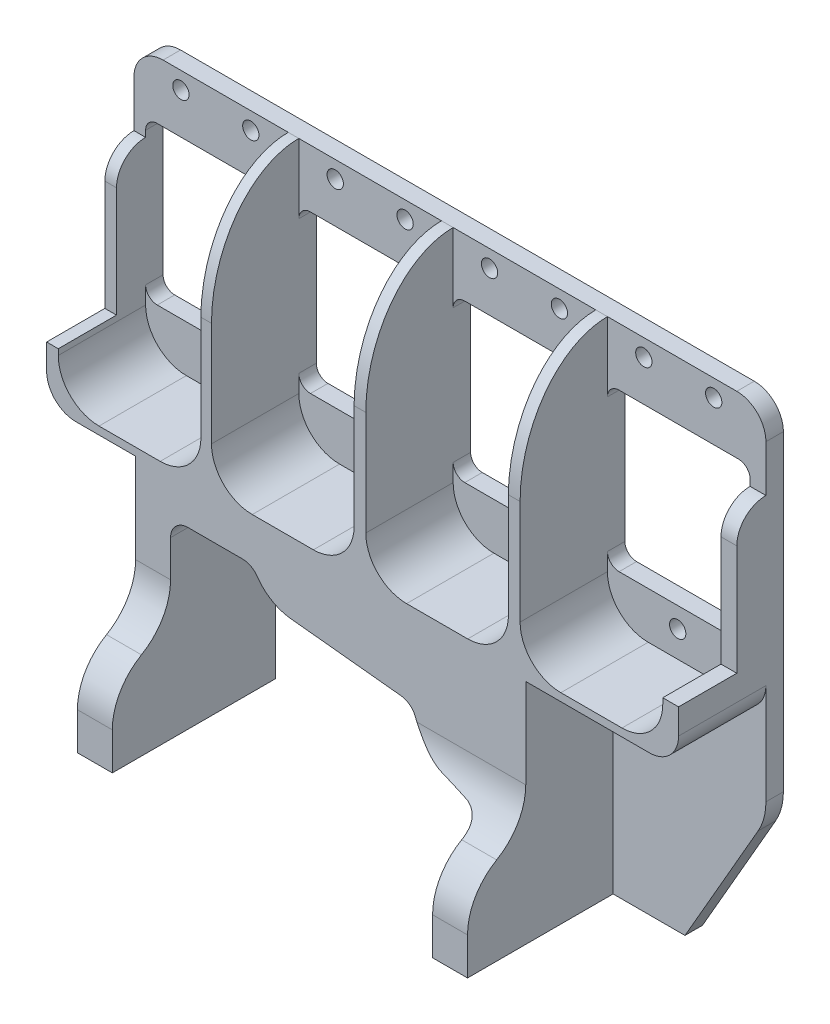
SolidWorks part; units mm, degrees
ref_plane "前视基准面" through (0, 0, 0) normal (0, 0, 1) x (1, 0, 0)
ref_plane "上视基准面" through (0, 0, 0) normal (0, 1, 0) x (1, 0, 0)
ref_plane "右视基准面" through (0, 0, 0) normal (1, 0, 0) x (0, 0, -1)
other "Configuration Table"
sketch "草图2" plane through (0, 0, 0) normal (0, 0, 1) x (1, 0, 0)
  line L0 (151.0633, 209.0132) -> (151.0476, 168.4956)
  line L1 (178.2976, 201.2948) -> (178.2976, 178.2948)
  line L2 (178.2976, 178.2948) -> (178.2976, 175.2948)
  line L3 (206.1919, 197.3972) -> (206.1919, 171.3972)
  line L4 (194.4691, 218.3694) -> (201.3108, 217.5164)
  line L5 (201.3108, 217.5164) -> (208.7441, 216.356)
  line L6 (166.5748, 222.2669) -> (173.4165, 221.4139)
  line L261 (199.1919, 164.3972) -> (192.9419, 164.3972)
  line L262 (237.2256, 158.3592) -> (242.1719, 178.962)
  line L263 (236.0401, 178.625) -> (234.6391, 165.2957)
  line L264 (225.8467, 158.1757) -> (217.3932, 159.0642)
  line L266 (210.2733, 167.8566) -> (212.2453, 186.6193)
  line L267 (252.608, 147.4673) -> (245.8094, 149.0995)
  line L268 (263.7227, 151.9978) -> (271.0421, 182.4855)
  line L269 (188.6919, 164.3972) -> (192.9419, 164.3972)
  line L270 (265.6404, 180.333) -> (245.7068, 185.1186)
  line L271 (252.8645, 197.798) -> (254.0666, 202.8051)
  line L272 (265.506, 196.9076) -> (265.0192, 194.88)
  line L273 (242.1719, 178.962) -> (243.2952, 183.6408)
  line L274 (187.6765, 215.8498) -> (187.692, 213.3583)
  line L275 (200.1917, 213.4362) -> (200.1725, 216.5198)
  line L276 (183.6919, 199.3972) -> (204.1919, 199.3972)
  line L278 (212.2623, 167.6475) -> (232.65, 165.5047)
  line L279 (220.5261, 208.0048) -> (221.0496, 212.986)
  line L280 (235.4723, 192.3568) -> (215.0846, 194.4996)
  line L281 (233.2553, 209.5307) -> (232.9576, 206.6982)
  line L282 (236.0401, 178.625) -> (237.2523, 190.1587)
  line L283 (212.8865, 192.7196) -> (212.2453, 186.6193)
  line L284 (183.6919, 172.3972) -> (204.1919, 172.3972)
  line L285 (239.4038, 158.8646) -> (259.3374, 154.079)
  line L286 (262.7567, 147.974) -> (251.8225, 127.8461)
  line L287 (263.7227, 151.9978) -> (262.7567, 147.974)
  line L288 (181.6919, 197.3972) -> (181.6919, 174.3972)
  line L289 (181.6919, 171.3972) -> (181.6919, 174.3972)
  line L290 (267.1183, 177.9214) -> (261.0487, 152.6398)
  line L291 (171.2976, 168.2948) -> (165.0476, 168.2948)
  line L293 (160.7976, 168.2948) -> (165.0476, 168.2948)
  line L295 (159.7822, 219.7473) -> (159.7977, 217.2558)
  line L296 (172.2974, 217.3337) -> (172.2782, 220.4173)
  line L297 (155.7976, 203.2948) -> (176.2976, 203.2948)
  line L300 (155.7976, 176.2948) -> (176.2976, 176.2948)
  line L301 (153.7976, 201.2948) -> (153.7976, 178.2948)
  line L302 (153.7976, 175.2948) -> (153.7976, 178.2948)
  line L303 (173.4165, 221.4139) -> (194.4691, 218.3694)
  line L304 (187.6765, 215.8498) -> (187.6765, 218.2449)
  line L305 (187.6765, 218.2449) -> (186.8438, 219.4721)
  line L306 (234.2789, 127.8461) -> (251.8225, 127.8461)
  line L307 (233.4789, 133.8446) -> (233.4789, 127.8461)
  line L308 (233.4789, 127.8461) -> (234.2789, 127.8461)
  line L309 (178.4789, 128.6348) -> (178.4789, 135.1402)
  line L310 (172.4789, 127.8461) -> (173.1594, 127.8461)
  line L311 (178.4789, 127.8461) -> (178.4789, 128.6348)
  line L312 (177.6789, 127.8461) -> (178.4789, 127.8461)
  line L313 (173.1594, 127.8461) -> (177.6789, 127.8461)
  line L314 (233.4789, 143.0663) -> (233.4789, 140.4276)
  line L315 (178.4789, 135.1402) -> (178.4789, 139.2823)
  line L316 (178.4789, 139.2823) -> (178.4789, 146.9191)
  line L317 (178.4789, 146.9191) -> (178.4789, 157.8461)
  line L318 (199.0973, 156.1096) -> (218.0428, 154.1184)
  line L319 (181.4789, 160.8461) -> (190.8607, 160.8461)
  line L320 (151.0476, 168.4956) -> (172.4789, 127.8461)
  arc A276 (237.2256, 158.3592) -> (238.6979, 152.1924) centre (244.0322, 156.725) ccw
  arc A277 (210.2733, 167.8566) -> (217.3932, 159.0642) centre (218.2295, 167.0204) ccw
  arc A278 (199.1919, 164.3972) -> (206.1919, 171.3972) centre (199.1919, 171.3972) ccw
  arc A279 (225.8467, 158.1757) -> (234.6391, 165.2957) centre (226.6829, 166.1319) ccw
  arc A281 (242.1719, 178.962) -> (242.2118, 179.1563) centre (239.2548, 179.6624) ccw
  arc A282 (212.2453, 186.6193) -> (212.2566, 186.7575) centre (209.2618, 186.9329) ccw
  arc A283 (236.0666, 178.8175) -> (236.0401, 178.625) centre (239.0236, 178.3114) ccw
  arc A284 (246.0441, 206.6986) -> (242.0035, 208.0676) centre (168.9419, -14.234) ccw
  arc A285 (220.2745, 214.0661) -> (208.7441, 216.356) centre (168.9419, -14.234) ccw
  arc A286 (252.608, 147.4673) -> (261.0487, 152.6398) centre (254.2421, 154.2739) ccw
  arc A287 (181.6919, 171.3972) -> (188.6919, 164.3972) centre (188.6919, 171.3972) ccw
  circle A288 centre (251.4735, 190.9331) radius 1.4
  circle A289 centre (263.142, 188.1317) radius 1.4
  arc A290 (267.1183, 177.9214) -> (265.6404, 180.333) centre (265.1735, 178.3883) ccw
  arc A291 (245.7068, 185.1186) -> (243.2952, 183.6408) centre (245.2399, 183.1739) ccw
  arc A292 (254.0666, 202.8051) -> (253.4554, 203.971) centre (253.0943, 203.0385) ccw
  arc A293 (252.8645, 197.798) -> (265.0192, 194.88) centre (258.9419, 196.339) ccw
  arc A294 (267.1505, 197.4145) -> (265.506, 196.9076) centre (266.4783, 196.6741) ccw
  arc A295 (253.4554, 203.971) -> (246.0441, 206.6986) centre (168.9419, -14.234) ccw
  arc A296 (271.7032, 188.063) -> (267.1505, 197.4145) centre (257.74, 187.0491) ccw
  arc A297 (187.692, 213.3583) -> (200.1917, 213.4362) centre (193.9419, 213.3972) ccw
  arc A298 (201.3108, 217.5164) -> (200.1725, 216.5198) centre (201.1725, 216.526) ccw
  arc A299 (206.1919, 197.3972) -> (204.1919, 199.3972) centre (204.1919, 197.3972) ccw
  arc A300 (183.6919, 199.3972) -> (181.6919, 197.3972) centre (183.6919, 197.3972) ccw
  circle A301 centre (199.9419, 206.3972) radius 1.4
  circle A302 centre (187.9419, 206.3972) radius 1.4
  arc A304 (210.4824, 169.8456) -> (212.2623, 167.6475) centre (212.4714, 169.6366) ccw
  arc A305 (232.65, 165.5047) -> (234.8481, 167.2847) centre (232.8591, 167.4938) ccw
  circle A306 centre (222.0903, 163.0953) radius 1.4
  arc A307 (220.5261, 208.0048) -> (232.9576, 206.6982) centre (226.7419, 207.3515) ccw
  circle A308 centre (220.043, 201.017) radius 1.4
  circle A309 centre (231.9773, 199.7627) radius 1.4
  arc A310 (237.2523, 190.1587) -> (235.4723, 192.3568) centre (235.2632, 190.3678) ccw
  arc A311 (221.0496, 212.986) -> (220.2745, 214.0661) centre (220.0551, 213.0905) ccw
  arc A312 (234.5301, 210.386) -> (233.2553, 209.5307) centre (234.2498, 209.4261) ccw
  arc A313 (215.0846, 194.4996) -> (212.8865, 192.7196) centre (214.8756, 192.5106) ccw
  arc A314 (242.0038, 208.0674) -> (234.5301, 210.386) centre (168.9419, -14.234) ccw
  arc A315 (204.1919, 172.3972) -> (206.1919, 174.3972) centre (204.1919, 174.3972) ccw
  circle A316 centre (193.9419, 168.8972) radius 1.4
  arc A317 (181.6919, 174.3972) -> (183.6919, 172.3972) centre (183.6919, 174.3972) ccw
  arc A318 (259.3374, 154.079) -> (261.749, 155.5569) centre (259.8043, 156.0238) ccw
  arc A319 (237.926, 161.2763) -> (239.4038, 158.8646) centre (239.8707, 160.8094) ccw
  circle A320 centre (248.5535, 153.0685) radius 1.4
  circle A321 centre (193.9419, 213.3972) radius 3.5
  circle A323 centre (258.9419, 196.339) radius 3.5
  arc A324 (263.3908, 199.858) -> (253.4554, 203.971) centre (168.9419, -14.234) ccw
  arc A325 (267.1505, 197.4145) -> (263.3908, 199.858) centre (257.74, 187.0491) ccw
  circle A326 centre (226.7419, 207.3515) radius 3.5
  arc A327 (234.5301, 210.386) -> (220.2745, 214.0661) centre (168.9419, -14.234) ccw
  arc A328 (171.2976, 168.2948) -> (178.2976, 175.2948) centre (171.2976, 175.2948) ccw
  arc A331 (153.7976, 175.2948) -> (160.7976, 168.2948) centre (160.7976, 175.2948) ccw
  arc A332 (159.7822, 219.7473) -> (158.3002, 220.6173) centre (158.7822, 219.7411) ccw
  arc A333 (159.7977, 217.2558) -> (172.2974, 217.3337) centre (166.0476, 217.2948) ccw
  arc A334 (173.4165, 221.4139) -> (172.2782, 220.4173) centre (173.2782, 220.4235) ccw
  arc A335 (178.2976, 201.2948) -> (176.2976, 203.2948) centre (176.2976, 201.2948) ccw
  arc A336 (155.7976, 203.2948) -> (153.7976, 201.2948) centre (155.7976, 201.2948) ccw
  circle A337 centre (172.0476, 210.2948) radius 1.4
  circle A338 centre (160.0476, 210.2948) radius 1.4
  arc A339 (158.3002, 220.6173) -> (152.4939, 214.5477) centre (165.0476, 208.3505) ccw
  arc A340 (176.2976, 176.2948) -> (178.2976, 178.2948) centre (176.2976, 178.2948) ccw
  circle A341 centre (166.0476, 172.7948) radius 1.4
  arc A342 (153.7976, 178.2948) -> (155.7976, 176.2948) centre (155.7976, 178.2948) ccw
  circle A343 centre (166.0476, 217.2948) radius 3.5
  arc A345 (166.5748, 222.2669) -> (158.3002, 220.6173) centre (165.0476, 208.3505) ccw
  arc A346 (220.5415, 152.1792) -> (221.76, 150.0096) centre (228.0411, 154.9641) ccw
  arc A347 (193.3351, 159.5424) -> (199.0973, 156.1096) centre (199.9335, 164.0658) ccw
  arc A348 (220.5415, 152.1792) -> (218.0428, 154.1184) centre (217.7292, 151.1348) ccw
  arc A349 (193.3351, 159.5424) -> (190.8607, 160.8461) centre (190.8607, 157.8461) ccw
  arc A350 (181.4789, 160.8461) -> (178.4789, 157.8461) centre (181.4789, 157.8461) ccw
  spline S5 degree 3 poles (245.8094, 149.0995) (244.7023, 149.3653) (243.562, 149.639) (242.3981, 149.9185) knots 0 0 0 0 1 1 1 1
  spline S6 degree 3 poles (242.3981, 149.9185) (240.9661, 150.2604) (239.6561, 151.0615) (238.6979, 152.1924) knots 0 0 0 0 1 1 1 1
  spline S7 degree 3 poles (271.0421, 182.4855) (271.1468, 182.9215) (271.2515, 183.3575) (271.3531, 183.7809) knots 0 0 0 0 1 1 1 1
  spline S8 degree 3 poles (271.3531, 183.7809) (271.6392, 184.9581) (271.73, 186.0745) (271.7435, 187.2429) (271.7328, 187.5457) (271.7129, 187.9558) (271.7023, 188.0633) (271.7026, 188.063) knots 0 0 0 0 0.5 0.5 0.75 0.75 1 1 1 1
  spline S9 degree 3 poles (152.4939, 214.5476) (152.4935, 214.5473) (152.4251, 214.4133) (152.183, 213.882) (152.0119, 213.4848) (151.6571, 212.4716) (151.4748, 211.8536) (151.1955, 210.4931) (151.098, 209.7566) (151.0633, 209.0132) knots 0 0 0 0 0.25 0.25 0.5 0.5 0.75 0.75 1 1 1 1
  spline S10 degree 3 poles (233.4789, 140.4276) (233.4789, 138.7088) (233.4789, 136.2853) (233.4789, 133.8446) knots 0 0 0 0 1 1 1 1
  spline S11 degree 3 poles (233.2337, 144.2542) (233.3952, 143.8804) (233.4792, 143.4735) (233.4789, 143.0663) knots 0 0 0 0 1 1 1 1
  spline S12 degree 3 poles (231.1793, 145.9834) (231.6902, 145.8625) (232.1463, 145.6054) (232.8415, 144.9724) (233.0819, 144.6067) (233.2337, 144.2542) knots 0 0 0 0 0.5 0.5 1 1 1 1
  spline S13 degree 3 poles (226.1736, 147.1852) (227.9043, 146.7697) (229.5835, 146.3665) (231.1793, 145.9834) knots 0 0 0 0 1 1 1 1
  spline S14 degree 3 poles (221.76, 150.0096) (222.8696, 148.5987) (224.4447, 147.5969) (226.1736, 147.1852) knots 0 0 0 0 1 1 1 1
  point P0 (0, 0)
  line B0 (187.9419, 206.3972) -> (187.9419, 208.8972)
  line B1 (187.9419, 206.3972) -> (185.4419, 206.3972)
  line B2 (187.9419, 206.3972) -> (187.9419, 203.8972)
  line B3 (187.9419, 206.3972) -> (190.4419, 206.3972)
  line B4 (187.9419, 208.8972) -> (187.9419, 210.2972)
  line B5 (185.4419, 206.3972) -> (184.0419, 206.3972)
  line B6 (187.9419, 203.8972) -> (187.9419, 202.4972)
  line B7 (190.4419, 206.3972) -> (191.8419, 206.3972)
  line B8 (222.0903, 163.0953) -> (222.0903, 165.5953)
  line B9 (222.0903, 163.0953) -> (219.5903, 163.0953)
  line B10 (222.0903, 163.0953) -> (222.0903, 160.5953)
  line B11 (222.0903, 163.0953) -> (224.5903, 163.0953)
  line B12 (222.0903, 165.5953) -> (222.0903, 166.9953)
  line B13 (219.5903, 163.0953) -> (218.1903, 163.0953)
  line B14 (222.0903, 160.5953) -> (222.0903, 159.1953)
  line B15 (224.5903, 163.0953) -> (225.9903, 163.0953)
  line B16 (251.4735, 190.9331) -> (251.4735, 193.4331)
  line B17 (251.4735, 190.9331) -> (248.9735, 190.9331)
  line B18 (251.4735, 190.9331) -> (251.4735, 188.4331)
  line B19 (251.4735, 190.9331) -> (253.9735, 190.9331)
  line B20 (251.4735, 193.4331) -> (251.4735, 194.8331)
  line B21 (248.9735, 190.9331) -> (247.5735, 190.9331)
  line B22 (251.4735, 188.4331) -> (251.4735, 187.0331)
  line B23 (253.9735, 190.9331) -> (255.3735, 190.9331)
  line B24 (263.142, 188.1317) -> (263.142, 190.6317)
  line B25 (263.142, 188.1317) -> (260.642, 188.1317)
  line B26 (263.142, 188.1317) -> (263.142, 185.6317)
  line B27 (263.142, 188.1317) -> (265.642, 188.1317)
  line B28 (263.142, 190.6317) -> (263.142, 192.0317)
  line B29 (260.642, 188.1317) -> (259.242, 188.1317)
  line B30 (263.142, 185.6317) -> (263.142, 184.2317)
  line B31 (265.642, 188.1317) -> (267.042, 188.1317)
  line B32 (248.5535, 153.0685) -> (248.5535, 155.5685)
  line B33 (248.5535, 153.0685) -> (246.0535, 153.0685)
  line B34 (248.5535, 153.0685) -> (248.5535, 150.5685)
  line B35 (248.5535, 153.0685) -> (251.0535, 153.0685)
  line B36 (248.5535, 155.5685) -> (248.5535, 156.9685)
  line B37 (246.0535, 153.0685) -> (244.6535, 153.0685)
  line B38 (248.5535, 150.5685) -> (248.5535, 149.1685)
  line B39 (251.0535, 153.0685) -> (252.4535, 153.0685)
  line B40 (231.9773, 199.7627) -> (231.9773, 202.2627)
  line B41 (231.9773, 199.7627) -> (229.4773, 199.7627)
  line B42 (231.9773, 199.7627) -> (231.9773, 197.2627)
  line B43 (231.9773, 199.7627) -> (234.4773, 199.7627)
  line B44 (231.9773, 202.2627) -> (231.9773, 203.6627)
  line B45 (229.4773, 199.7627) -> (228.0773, 199.7627)
  line B46 (231.9773, 197.2627) -> (231.9773, 195.8627)
  line B47 (234.4773, 199.7627) -> (235.8773, 199.7627)
  line B48 (220.043, 201.017) -> (220.043, 203.517)
  line B49 (220.043, 201.017) -> (217.543, 201.017)
  line B50 (220.043, 201.017) -> (220.043, 198.517)
  line B51 (220.043, 201.017) -> (222.543, 201.017)
  line B52 (220.043, 203.517) -> (220.043, 204.917)
  line B53 (217.543, 201.017) -> (216.143, 201.017)
  line B54 (220.043, 198.517) -> (220.043, 197.117)
  line B55 (222.543, 201.017) -> (223.943, 201.017)
  line B56 (193.9419, 168.8972) -> (193.9419, 171.3972)
  line B57 (193.9419, 168.8972) -> (191.4419, 168.8972)
  line B58 (193.9419, 168.8972) -> (193.9419, 166.3972)
  line B59 (193.9419, 168.8972) -> (196.4419, 168.8972)
  line B60 (193.9419, 171.3972) -> (193.9419, 172.7972)
  line B61 (191.4419, 168.8972) -> (190.0419, 168.8972)
  line B62 (193.9419, 166.3972) -> (193.9419, 164.9972)
  line B63 (196.4419, 168.8972) -> (197.8419, 168.8972)
  line B64 (199.9419, 206.3972) -> (199.9419, 208.8972)
  line B65 (199.9419, 206.3972) -> (197.4419, 206.3972)
  line B66 (199.9419, 206.3972) -> (199.9419, 203.8972)
  line B67 (199.9419, 206.3972) -> (202.4419, 206.3972)
  line B68 (199.9419, 208.8972) -> (199.9419, 210.2972)
  line B69 (197.4419, 206.3972) -> (196.0419, 206.3972)
  line B70 (199.9419, 203.8972) -> (199.9419, 202.4972)
  line B71 (202.4419, 206.3972) -> (203.8419, 206.3972)
  line B72 (160.0476, 210.2948) -> (160.0476, 212.7948)
  line B73 (160.0476, 210.2948) -> (157.5476, 210.2948)
  line B74 (160.0476, 210.2948) -> (160.0476, 207.7948)
  line B75 (160.0476, 210.2948) -> (162.5476, 210.2948)
  line B76 (160.0476, 212.7948) -> (160.0476, 214.1948)
  line B77 (157.5476, 210.2948) -> (156.1476, 210.2948)
  line B78 (160.0476, 207.7948) -> (160.0476, 206.3948)
  line B79 (162.5476, 210.2948) -> (163.9476, 210.2948)
  line B80 (166.0476, 172.7948) -> (166.0476, 175.2948)
  line B81 (166.0476, 172.7948) -> (163.5476, 172.7948)
  line B82 (166.0476, 172.7948) -> (166.0476, 170.2948)
  line B83 (166.0476, 172.7948) -> (168.5476, 172.7948)
  line B84 (166.0476, 175.2948) -> (166.0476, 176.6948)
  line B85 (163.5476, 172.7948) -> (162.1476, 172.7948)
  line B86 (166.0476, 170.2948) -> (166.0476, 168.8948)
  line B87 (168.5476, 172.7948) -> (169.9476, 172.7948)
  line B88 (172.0476, 210.2948) -> (172.0476, 212.7948)
  line B89 (172.0476, 210.2948) -> (169.5476, 210.2948)
  line B90 (172.0476, 210.2948) -> (172.0476, 207.7948)
  line B91 (172.0476, 210.2948) -> (174.5476, 210.2948)
  line B92 (172.0476, 212.7948) -> (172.0476, 214.1948)
  line B93 (169.5476, 210.2948) -> (168.1476, 210.2948)
  line B94 (172.0476, 207.7948) -> (172.0476, 206.3948)
  line B95 (174.5476, 210.2948) -> (175.9476, 210.2948)
sketch_block_instance "SW_CENTERMARKSYMBOL_3-1"
sketch_block "SW_CENTERMARKSYMBOL_3"
sketch_block_instance "SW_CENTERMARKSYMBOL_4-1"
sketch_block "SW_CENTERMARKSYMBOL_4"
sketch_block_instance "SW_CENTERMARKSYMBOL_5-1"
sketch_block "SW_CENTERMARKSYMBOL_5"
sketch_block_instance "SW_CENTERMARKSYMBOL_6-1"
sketch_block "SW_CENTERMARKSYMBOL_6"
sketch_block_instance "SW_CENTERMARKSYMBOL_7-1"
sketch_block "SW_CENTERMARKSYMBOL_7"
sketch_block_instance "SW_CENTERMARKSYMBOL_8-1"
sketch_block "SW_CENTERMARKSYMBOL_8"
sketch_block_instance "SW_CENTERMARKSYMBOL_9-1"
sketch_block "SW_CENTERMARKSYMBOL_9"
sketch_block_instance "SW_CENTERMARKSYMBOL_10-1"
sketch_block "SW_CENTERMARKSYMBOL_10"
sketch_block_instance "SW_CENTERMARKSYMBOL_11-1"
sketch_block "SW_CENTERMARKSYMBOL_11"
sketch_block_instance "SW_CENTERMARKSYMBOL_3-2"
sketch_block_instance "SW_CENTERMARKSYMBOL_10-2"
sketch_block_instance "SW_CENTERMARKSYMBOL_11-2"
ref_plane "基准面2" through (0, 0, 15.8251) normal (0, 0, 1) x (1, 0, 0)
sketch "草图12" plane through (0, 0, 15.8251) normal (0, 0, 1) x (1, 0, 0)
  line L2 (157.1945, 213.2289) -> (265.7227, 213.2289)
  line L5 (265.7227, 213.2289) -> (265.7227, 151.9978)
  line L6 (157.1945, 156.8365) -> (172.4789, 127.8461)
  line L9 (251.8225, 127.8461) -> (233.4789, 127.8461)
  line L10 (233.4789, 127.8461) -> (233.4789, 143.0663)
  line L11 (172.4789, 127.8461) -> (178.4789, 127.8461)
  line L12 (178.4789, 127.8461) -> (178.4789, 157.8461)
  line L13 (181.4789, 160.8461) -> (190.8607, 160.8461)
  line L14 (199.0973, 156.1096) -> (218.0428, 154.1184)
  line L15 (226.1736, 147.1852) -> (231.1793, 145.9834)
  line L23 (187.5086, 203.2948) -> (208.0086, 203.2948)
  line L24 (210.0086, 201.2948) -> (210.0086, 178.2948)
  line L25 (208.0086, 176.2948) -> (187.5086, 176.2948)
  line L26 (185.5086, 178.2948) -> (185.5086, 201.2948)
  line L27 (185.5086, 178.2948) -> (185.5086, 175.2948)
  line L28 (210.0086, 178.2948) -> (210.0086, 175.2948)
  line L29 (192.5086, 168.2948) -> (203.0086, 168.2948)
  line L30 (265.7227, 151.9978) -> (251.8225, 127.8461)
  line L51 (214.0086, 203.2948) -> (234.5086, 203.2948)
  line L52 (236.5086, 201.2948) -> (236.5086, 178.2948)
  line L53 (234.5086, 176.2948) -> (214.0086, 176.2948)
  line L54 (212.0086, 178.2948) -> (212.0086, 201.2948)
  line L55 (212.0086, 178.2948) -> (212.0086, 175.2948)
  line L56 (236.5086, 178.2948) -> (236.5086, 175.2948)
  line L57 (219.0086, 168.2948) -> (229.5086, 168.2948)
  line L60 (161.1945, 203.2948) -> (181.6945, 203.2948)
  line L61 (183.6945, 201.2948) -> (183.6945, 178.2948)
  line L62 (181.6945, 176.2948) -> (161.1945, 176.2948)
  line L63 (159.1945, 178.2948) -> (159.1945, 201.2948)
  line L64 (159.1945, 178.2948) -> (159.1945, 175.2948)
  line L65 (183.6945, 178.2948) -> (183.6945, 175.2948)
  line L66 (166.1945, 168.2948) -> (176.6945, 168.2948)
  line L68 (157.1945, 213.2289) -> (157.1945, 156.8365)
  line L69 (236.5086, 201.2948) -> (236.5086, 178.2948)
  line L70 (236.5086, 178.2948) -> (236.5086, 175.2948)
  line L72 (240.5086, 203.2948) -> (261.0086, 203.2948)
  line L73 (263.0086, 201.2948) -> (263.0086, 178.2948)
  line L74 (261.0086, 176.2948) -> (240.5086, 176.2948)
  line L75 (238.5086, 178.2948) -> (238.5086, 201.2948)
  line L76 (238.5086, 178.2948) -> (238.5086, 175.2948)
  line L77 (263.0086, 178.2948) -> (263.0086, 175.2948)
  line L78 (245.5086, 168.2948) -> (256.0086, 168.2948)
  line L83 (325.7181, 277.8251) -> (346.2181, 277.8251)
  line L84 (348.2181, 275.8251) -> (348.2181, 252.8251)
  line L85 (346.2181, 250.8251) -> (325.7181, 250.8251)
  line L86 (323.7181, 252.8251) -> (323.7181, 275.8251)
  line L87 (323.7181, 252.8251) -> (323.7181, 249.8251)
  line L88 (348.2181, 252.8251) -> (348.2181, 249.8251)
  line L89 (330.7181, 242.8251) -> (341.2181, 242.8251)
  line L91 (352.2181, 277.8251) -> (372.7181, 277.8251)
  line L92 (374.7181, 275.8251) -> (374.7181, 252.8251)
  line L93 (372.7181, 250.8251) -> (352.2181, 250.8251)
  line L94 (350.2181, 252.8251) -> (350.2181, 275.8251)
  line L95 (350.2181, 252.8251) -> (350.2181, 249.8251)
  line L96 (374.7181, 252.8251) -> (374.7181, 249.8251)
  line L97 (357.2181, 242.8251) -> (367.7181, 242.8251)
  line L98 (299.404, 277.8251) -> (319.904, 277.8251)
  line L100 (319.904, 250.8251) -> (299.404, 250.8251)
  line L102 (297.404, 252.8251) -> (297.404, 249.8251)
  line L103 (321.904, 252.8251) -> (321.904, 249.8251)
  line L104 (304.404, 242.8251) -> (314.904, 242.8251)
  line L106 (374.7181, 275.8251) -> (374.7181, 252.8251)
  line L107 (374.7181, 252.8251) -> (374.7181, 249.8251)
  line L108 (378.7181, 277.8251) -> (399.2181, 277.8251)
  line L109 (401.2181, 275.8251) -> (401.2181, 252.8251)
  line L110 (399.2181, 250.8251) -> (378.7181, 250.8251)
  line L111 (376.7181, 252.8251) -> (376.7181, 275.8251)
  line L112 (376.7181, 252.8251) -> (376.7181, 249.8251)
  line L113 (401.2181, 252.8251) -> (401.2181, 249.8251)
  line L114 (383.7181, 242.8251) -> (394.2181, 242.8251)
  arc A4 (181.4789, 160.8461) -> (178.4789, 157.8461) centre (181.4789, 157.8461) ccw
  arc A8 (193.3351, 159.5424) -> (190.8607, 160.8461) centre (190.8607, 157.8461) ccw
  arc A9 (193.3351, 159.5424) -> (199.0973, 156.1096) centre (199.9335, 164.0658) ccw
  arc A10 (220.5415, 152.1792) -> (218.0428, 154.1184) centre (217.7292, 151.1348) ccw
  arc A11 (220.5415, 152.1792) -> (226.1736, 147.1852) centre (228.0411, 154.9641) ccw
  circle A15 centre (191.7586, 210.2948) radius 1.4
  circle A16 centre (203.7586, 210.2948) radius 1.4
  arc A28 (187.5086, 203.2948) -> (185.5086, 201.2948) centre (187.5086, 201.2948) ccw
  arc A30 (210.0086, 201.2948) -> (208.0086, 203.2948) centre (208.0086, 201.2948) ccw
  arc A31 (185.5086, 178.2948) -> (187.5086, 176.2948) centre (187.5086, 178.2948) ccw
  arc A32 (208.0086, 176.2948) -> (210.0086, 178.2948) centre (208.0086, 178.2948) ccw
  circle A33 centre (197.7586, 172.7948) radius 1.4
  arc A34 (185.5086, 175.2948) -> (192.5086, 168.2948) centre (192.5086, 175.2948) ccw
  arc A35 (203.0086, 168.2948) -> (210.0086, 175.2948) centre (203.0086, 175.2948) ccw
  circle A51 centre (218.2586, 210.2948) radius 1.4
  circle A52 centre (230.2586, 210.2948) radius 1.4
  arc A53 (214.0086, 203.2948) -> (212.0086, 201.2948) centre (214.0086, 201.2948) ccw
  arc A54 (236.5086, 201.2948) -> (234.5086, 203.2948) centre (234.5086, 201.2948) ccw
  arc A55 (212.0086, 178.2948) -> (214.0086, 176.2948) centre (214.0086, 178.2948) ccw
  arc A56 (234.5086, 176.2948) -> (236.5086, 178.2948) centre (234.5086, 178.2948) ccw
  circle A57 centre (224.2586, 172.7948) radius 1.4
  arc A58 (212.0086, 175.2948) -> (219.0086, 168.2948) centre (219.0086, 175.2948) ccw
  arc A59 (229.5086, 168.2948) -> (236.5086, 175.2948) centre (229.5086, 175.2948) ccw
  arc A60 (161.1945, 203.2948) -> (159.1945, 201.2948) centre (161.1945, 201.2948) ccw
  arc A61 (183.6945, 201.2948) -> (181.6945, 203.2948) centre (181.6945, 201.2948) ccw
  arc A62 (159.1945, 178.2948) -> (161.1945, 176.2948) centre (161.1945, 178.2948) ccw
  arc A63 (181.6945, 176.2948) -> (183.6945, 178.2948) centre (181.6945, 178.2948) ccw
  circle A64 centre (171.2586, 172.7948) radius 1.4
  arc A65 (159.1945, 175.2948) -> (166.1945, 168.2948) centre (166.1945, 175.2948) ccw
  arc A66 (176.6945, 168.2948) -> (183.6945, 175.2948) centre (176.6945, 175.2948) ccw
  circle A67 centre (244.7586, 210.2948) radius 1.4
  circle A68 centre (256.7586, 210.2948) radius 1.4
  arc A69 (240.5086, 203.2948) -> (238.5086, 201.2948) centre (240.5086, 201.2948) ccw
  arc A70 (263.0086, 201.2948) -> (261.0086, 203.2948) centre (261.0086, 201.2948) ccw
  arc A71 (238.5086, 178.2948) -> (240.5086, 176.2948) centre (240.5086, 178.2948) ccw
  arc A72 (261.0086, 176.2948) -> (263.0086, 178.2948) centre (261.0086, 178.2948) ccw
  circle A73 centre (250.7586, 172.7948) radius 1.4
  arc A74 (238.5086, 175.2948) -> (245.5086, 168.2948) centre (245.5086, 175.2948) ccw
  arc A75 (256.0086, 168.2948) -> (263.0086, 175.2948) centre (256.0086, 175.2948) ccw
  circle A76 centre (165.2586, 210.2948) radius 1.4
  circle A77 centre (177.2586, 210.2948) radius 1.4
  arc A85 (325.7181, 277.8251) -> (323.7181, 275.8251) centre (325.7181, 275.8251) ccw
  arc A86 (348.2181, 275.8251) -> (346.2181, 277.8251) centre (346.2181, 275.8251) ccw
  arc A87 (323.7181, 252.8251) -> (325.7181, 250.8251) centre (325.7181, 252.8251) ccw
  arc A88 (346.2181, 250.8251) -> (348.2181, 252.8251) centre (346.2181, 252.8251) ccw
  circle A89 centre (335.9681, 247.3251) radius 1.4
  arc A90 (323.7181, 249.8251) -> (330.7181, 242.8251) centre (330.7181, 249.8251) ccw
  arc A91 (341.2181, 242.8251) -> (348.2181, 249.8251) centre (341.2181, 249.8251) ccw
  arc A94 (352.2181, 277.8251) -> (350.2181, 275.8251) centre (352.2181, 275.8251) ccw
  arc A95 (374.7181, 275.8251) -> (372.7181, 277.8251) centre (372.7181, 275.8251) ccw
  arc A96 (350.2181, 252.8251) -> (352.2181, 250.8251) centre (352.2181, 252.8251) ccw
  arc A97 (372.7181, 250.8251) -> (374.7181, 252.8251) centre (372.7181, 252.8251) ccw
  circle A98 centre (362.4681, 247.3251) radius 1.4
  arc A99 (350.2181, 249.8251) -> (357.2181, 242.8251) centre (357.2181, 249.8251) ccw
  arc A100 (367.7181, 242.8251) -> (374.7181, 249.8251) centre (367.7181, 249.8251) ccw
  arc A101 (299.404, 277.8251) -> (297.404, 275.8251) centre (299.404, 275.8251) ccw
  arc A102 (321.904, 275.8251) -> (319.904, 277.8251) centre (319.904, 275.8251) ccw
  arc A103 (297.404, 252.8251) -> (299.404, 250.8251) centre (299.404, 252.8251) ccw
  arc A104 (319.904, 250.8251) -> (321.904, 252.8251) centre (319.904, 252.8251) ccw
  circle A105 centre (309.4681, 247.3251) radius 1.4
  arc A106 (297.404, 249.8251) -> (304.404, 242.8251) centre (304.404, 249.8251) ccw
  arc A107 (314.904, 242.8251) -> (321.904, 249.8251) centre (314.904, 249.8251) ccw
  arc A110 (378.7181, 277.8251) -> (376.7181, 275.8251) centre (378.7181, 275.8251) ccw
  arc A111 (401.2181, 275.8251) -> (399.2181, 277.8251) centre (399.2181, 275.8251) ccw
  arc A112 (376.7181, 252.8251) -> (378.7181, 250.8251) centre (378.7181, 252.8251) ccw
  arc A113 (399.2181, 250.8251) -> (401.2181, 252.8251) centre (399.2181, 252.8251) ccw
  circle A114 centre (388.9681, 247.3251) radius 1.4
  arc A115 (376.7181, 249.8251) -> (383.7181, 242.8251) centre (383.7181, 249.8251) ccw
  arc A116 (394.2181, 242.8251) -> (401.2181, 249.8251) centre (394.2181, 249.8251) ccw
  spline S1 degree 2 poles (231.1793, 145.9834) (233.4263, 145.1786) (233.4789, 143.0663) knots 0 0 0 1 1 1
extrude "凸台-拉伸1" add sketch "草图12" along normal blind 3 contours L15 S1 L10 L9 L30 L5 L2 L68 L6 L11 L12 A4 L13 A8 A9 L14 A10 A11 A15 A16 A35 L29 A34 L27 L26 A28 L23 A30 L24 L28 A51 A52 A59 L57 A58 L55 L54 A53 L51 A54 L52 L56 A66 L66 region at (211.4586, 211.848, 15.8251)
sketch "草图23" plane through (0, 0, 18.8251) normal (0, 0, 1) x (1, 0, 0)
  line L0 (181.6945, 176.2948) -> (161.1945, 176.2948)
  line L1 (159.1945, 178.2948) -> (159.1945, 175.2948)
  line L2 (183.6945, 178.2948) -> (183.6945, 175.2948)
  line L3 (166.1945, 168.2948) -> (176.6945, 168.2948)
  line L5 (261.0086, 176.2948) -> (240.5086, 176.2948)
  line L11 (208.0086, 176.2948) -> (187.5086, 176.2948)
  line L12 (185.5086, 178.2948) -> (185.5086, 175.2948)
  line L13 (210.0086, 178.2948) -> (210.0086, 175.2948)
  line L14 (192.5086, 168.2948) -> (203.0086, 168.2948)
  line L15 (234.5086, 176.2948) -> (214.0086, 176.2948)
  line L16 (212.0086, 178.2948) -> (212.0086, 175.2948)
  line L17 (236.5086, 178.2948) -> (236.5086, 175.2948)
  line L18 (219.0086, 168.2948) -> (229.5086, 168.2948)
  line L19 (238.5086, 178.2948) -> (238.5086, 175.2948)
  line L20 (263.0086, 178.2948) -> (263.0086, 175.2948)
  line L21 (245.5086, 168.2948) -> (256.0086, 168.2948)
  arc A0 (159.1945, 178.2948) -> (161.1945, 176.2948) centre (161.1945, 178.2948) ccw
  arc A1 (181.6945, 176.2948) -> (183.6945, 178.2948) centre (181.6945, 178.2948) ccw
  circle A2 centre (171.2586, 172.7948) radius 1.4
  arc A3 (159.1945, 175.2948) -> (166.1945, 168.2948) centre (166.1945, 175.2948) ccw
  arc A4 (176.6945, 168.2948) -> (183.6945, 175.2948) centre (176.6945, 175.2948) ccw
  arc A5 (185.5086, 178.2948) -> (187.5086, 176.2948) centre (187.5086, 178.2948) ccw
  arc A6 (208.0086, 176.2948) -> (210.0086, 178.2948) centre (208.0086, 178.2948) ccw
  circle A7 centre (197.5727, 172.7948) radius 1.4
  arc A8 (185.5086, 175.2948) -> (192.5086, 168.2948) centre (192.5086, 175.2948) ccw
  arc A9 (203.0086, 168.2948) -> (210.0086, 175.2948) centre (203.0086, 175.2948) ccw
  arc A10 (212.0086, 178.2948) -> (214.0086, 176.2948) centre (214.0086, 178.2948) ccw
  arc A11 (234.5086, 176.2948) -> (236.5086, 178.2948) centre (234.5086, 178.2948) ccw
  circle A12 centre (224.0727, 172.7948) radius 1.4
  arc A13 (212.0086, 175.2948) -> (219.0086, 168.2948) centre (219.0086, 175.2948) ccw
  arc A14 (229.5086, 168.2948) -> (236.5086, 175.2948) centre (229.5086, 175.2948) ccw
  arc A15 (238.5086, 178.2948) -> (240.5086, 176.2948) centre (240.5086, 178.2948) ccw
  arc A16 (261.0086, 176.2948) -> (263.0086, 178.2948) centre (261.0086, 178.2948) ccw
  circle A17 centre (250.5727, 172.7948) radius 1.4
  arc A18 (238.5086, 175.2948) -> (245.5086, 168.2948) centre (245.5086, 175.2948) ccw
  arc A19 (256.0086, 168.2948) -> (263.0086, 175.2948) centre (256.0086, 175.2948) ccw
extrude "凸台-拉伸2" add sketch "草图23" against normal blind 3
sketch "草图24" plane through (0, 0, 18.8251) normal (0, 0, 1) x (1, 0, 0)
  line L0 (157.1945, 213.2289) -> (157.1945, 156.8365) construction
  line L1 (157.1945, 200.2299) -> (159.1945, 200.2299)
  line L2 (157.1945, 200.2299) -> (157.1945, 166.9524)
  line L4 (159.1945, 200.2299) -> (159.1945, 175.2948)
  line L6 (265.7227, 213.2289) -> (265.7227, 151.9978) construction
  line L9 (265.7227, 200.2299) -> (263.0086, 200.2299)
  line L10 (265.7227, 200.2299) -> (265.7227, 166.9524)
  line L12 (263.0086, 200.2299) -> (263.0086, 175.2948)
  line L14 (183.6945, 213.2289) -> (185.5086, 213.2289)
  line L16 (157.1945, 213.2289) -> (265.7227, 213.2289) construction
  line L19 (210.0086, 213.2289) -> (210.0086, 175.2948)
  line L21 (212.0086, 213.2289) -> (212.0086, 175.2948)
  line L23 (210.0086, 213.2289) -> (212.0086, 213.2289)
  line L24 (159.1945, 178.2948) -> (159.1945, 175.2948)
  line L26 (236.5086, 213.2289) -> (236.5086, 175.2948)
  line L28 (238.5086, 213.2289) -> (238.5086, 175.2948)
  line L29 (236.5086, 213.2289) -> (238.5086, 213.2289)
  line L30 (166.1945, 168.2948) -> (176.6945, 168.2948)
  line L35 (183.6945, 178.2948) -> (183.6945, 175.2948)
  line L36 (166.1945, 168.2948) -> (176.6945, 168.2948)
  line L38 (185.5086, 178.2948) -> (185.5086, 175.2948)
  line L43 (210.0086, 178.2948) -> (210.0086, 175.2948)
  line L44 (192.5086, 168.2948) -> (203.0086, 168.2948)
  line L46 (212.0086, 178.2948) -> (212.0086, 175.2948)
  line L47 (236.5086, 178.2948) -> (236.5086, 175.2948)
  line L48 (219.0086, 168.2948) -> (229.5086, 168.2948)
  line L50 (238.5086, 178.2948) -> (238.5086, 175.2948)
  line L51 (263.0086, 178.2948) -> (263.0086, 175.2948)
  line L52 (245.5086, 168.2948) -> (256.0086, 168.2948)
  line L53 (192.5086, 168.2948) -> (203.0086, 168.2948)
  line L55 (159.1945, 200.2299) -> (159.1945, 178.2948)
  line L56 (183.6945, 175.2948) -> (183.6945, 213.2289)
  line L57 (185.5086, 175.2948) -> (185.5086, 213.2289)
  line L58 (265.7227, 166.9524) -> (157.1945, 166.9524)
  line L59 (219.0086, 168.2948) -> (229.5086, 168.2948)
  line L60 (245.5086, 168.2948) -> (256.0086, 168.2948)
  circle A7 centre (171.2586, 172.7948) radius 1.4
  arc A8 (159.1945, 175.2948) -> (166.1945, 168.2948) centre (166.1945, 175.2948) ccw
  arc A9 (176.6945, 168.2948) -> (183.6945, 175.2948) centre (176.6945, 175.2948) ccw
  circle A17 centre (197.5727, 172.7948) radius 1.4
  arc A18 (185.5086, 175.2948) -> (192.5086, 168.2948) centre (192.5086, 175.2948) ccw
  arc A19 (203.0086, 168.2948) -> (210.0086, 175.2948) centre (203.0086, 175.2948) ccw
  circle A22 centre (224.0727, 172.7948) radius 1.4
  arc A23 (212.0086, 175.2948) -> (219.0086, 168.2948) centre (219.0086, 175.2948) ccw
  arc A24 (229.5086, 168.2948) -> (236.5086, 175.2948) centre (229.5086, 175.2948) ccw
  circle A27 centre (250.5727, 172.7948) radius 1.4
  arc A28 (238.5086, 175.2948) -> (245.5086, 168.2948) centre (245.5086, 175.2948) ccw
  arc A29 (256.0086, 168.2948) -> (263.0086, 175.2948) centre (256.0086, 175.2948) ccw
extrude "凸台-拉伸3" add sketch "草图24" along normal blind 15 contours A29 L52 A28 L28 L29 L26 A24 L48 A23 L21 L23 L19 A19 L44 A18 L38 L57 L14 L56 L35 A9 L30 A8 L4 L1 L2 L58 L10 L9 L12 region at (158.1945, 199.05, 18.8251)
sketch "草图25" plane through (0, 0, 18.8251) normal (0, 0, 1) x (1, 0, 0)
  line L4 (172.4789, 127.8461) -> (172.4789, 166.9524)
  line L5 (239.4789, 127.8461) -> (239.4789, 166.9524)
  line L16 (265.7227, 166.9524) -> (157.1945, 166.9524)
  line L17 (157.1945, 166.9524) -> (157.1945, 156.8365)
  line L18 (157.1945, 156.8365) -> (172.4789, 127.8461)
  line L19 (172.4789, 127.8461) -> (178.4789, 127.8461)
  line L20 (178.4789, 127.8461) -> (178.4789, 157.8461)
  line L21 (181.4789, 160.8461) -> (190.8607, 160.8461)
  line L22 (199.0973, 156.1096) -> (218.0428, 154.1184)
  line L23 (226.1736, 147.1852) -> (231.1793, 145.9834)
  line L24 (233.4789, 143.0663) -> (233.4789, 127.8461)
  line L25 (233.4789, 127.8461) -> (251.8225, 127.8461)
  line L26 (251.8225, 127.8461) -> (265.7227, 151.9978)
  line L27 (265.7227, 151.9978) -> (265.7227, 166.9524)
  line L28 (239.4789, 166.9524) -> (172.4789, 166.9524)
  line L31 (172.4789, 127.8461) -> (178.4789, 127.8461)
  line L32 (178.4789, 127.8461) -> (178.4789, 157.8461)
  line L33 (181.4789, 160.8461) -> (190.8607, 160.8461)
  line L34 (199.0973, 156.1096) -> (218.0428, 154.1184)
  line L35 (226.1736, 147.1852) -> (231.1793, 145.9834)
  line L36 (233.4789, 143.0663) -> (233.4789, 127.8461)
  line L37 (233.4789, 127.8461) -> (239.4789, 127.8461)
  arc A5 (181.4789, 160.8461) -> (178.4789, 157.8461) centre (181.4789, 157.8461) ccw
  arc A6 (193.3351, 159.5424) -> (190.8607, 160.8461) centre (190.8607, 157.8461) ccw
  arc A7 (193.3351, 159.5424) -> (199.0973, 156.1096) centre (199.9335, 164.0658) ccw
  arc A8 (220.5415, 152.1792) -> (218.0428, 154.1184) centre (217.7292, 151.1348) ccw
  arc A9 (220.5415, 152.1792) -> (226.1736, 147.1852) centre (228.0411, 154.9641) ccw
  arc A10 (181.4789, 160.8461) -> (178.4789, 157.8461) centre (181.4789, 157.8461) ccw
  arc A11 (193.3351, 159.5424) -> (190.8607, 160.8461) centre (190.8607, 157.8461) ccw
  arc A12 (193.3351, 159.5424) -> (199.0973, 156.1096) centre (199.9335, 164.0658) ccw
  arc A13 (220.5415, 152.1792) -> (218.0428, 154.1184) centre (217.7292, 151.1348) ccw
  arc A14 (220.5415, 152.1792) -> (226.1736, 147.1852) centre (228.0411, 154.9641) ccw
  parabola Q1 (231.1793, 145.9834) -> (233.4789, 143.0663) focus (231.9347, 143.8851) apex (233.0753, 144.5646)
  parabola Q2 (231.1793, 145.9834) -> (233.4789, 143.0663) focus (231.9347, 143.8851) apex (233.0753, 144.5646)
  dimension "D1" = 0
extrude "凸台-拉伸4" add sketch "草图25" along normal blind 25
sketch "草图26" plane through (0, 0, 33.8251) normal (0, 0, 1) x (1, 0, 0)
  line L0 (159.1945, 200.2299) -> (159.1945, 175.2948) construction
  line L1 (157.1945, 200.2299) -> (159.1945, 200.2299)
  line L2 (157.1945, 200.2299) -> (157.1945, 176.2948)
  line L3 (157.1945, 176.2948) -> (159.1945, 176.2948)
  line L4 (159.1945, 200.2299) -> (159.1945, 176.2948)
  line L5 (265.7227, 200.2299) -> (265.7227, 166.9524) construction
  line L6 (263.0086, 200.2299) -> (265.7227, 200.2299)
  line L7 (263.0086, 200.2299) -> (263.0086, 176.2948)
  line L8 (263.0086, 176.2948) -> (265.7227, 176.2948)
  line L9 (265.7227, 200.2299) -> (265.7227, 176.2948)
extrude "切除-拉伸1" cut sketch "草图26" against normal blind 10
sketch "草图27" plane through (172.4789, 0, 0) normal (-1, 0, 0) x (0, 0, 1)
  line L0 (43.8251, 166.9524) -> (43.8251, 127.8461) construction
  line L1 (33.8251, 166.9524) -> (43.8251, 166.9524)
  line L2 (33.8251, 166.9524) -> (33.8251, 144.2513)
  line L3 (33.8251, 144.2513) -> (43.8251, 144.2513)
  line L4 (43.8251, 166.9524) -> (43.8251, 144.2513)
extrude "切除-拉伸2" cut sketch "草图27" against normal blind 82
fillet "圆角1" radius 10 2 edges at (236.357, 144.2513, 43.8251) (175.4789, 144.2513, 43.8251)
fillet "圆角2" radius 10 2 edges at (236.357, 144.2513, 33.8251) (175.4789, 144.2513, 33.8251)
fillet "圆角3" radius 10 2 edges at (265.7227, 151.9978, 17.3251) (157.1945, 156.8365, 17.3251)
fillet "圆角4" radius 20 3 edges at (237.5086, 213.2289, 33.8251) (211.0086, 213.2289, 33.8251) (184.6015, 213.2289, 33.8251) second distance 15 first distance on face at (207.6979, 173.1196, 33.8251)
fillet "圆角5" radius 5 4 edges at (264.3656, 200.2299, 23.8251) (158.1945, 200.2299, 23.8251) (265.7227, 213.2289, 17.3251) (157.1945, 213.2289, 17.3251)
fillet "圆角6" radius 5 2 edges at (265.7227, 166.9524, 26.3251) (157.1945, 166.9524, 26.3251)
